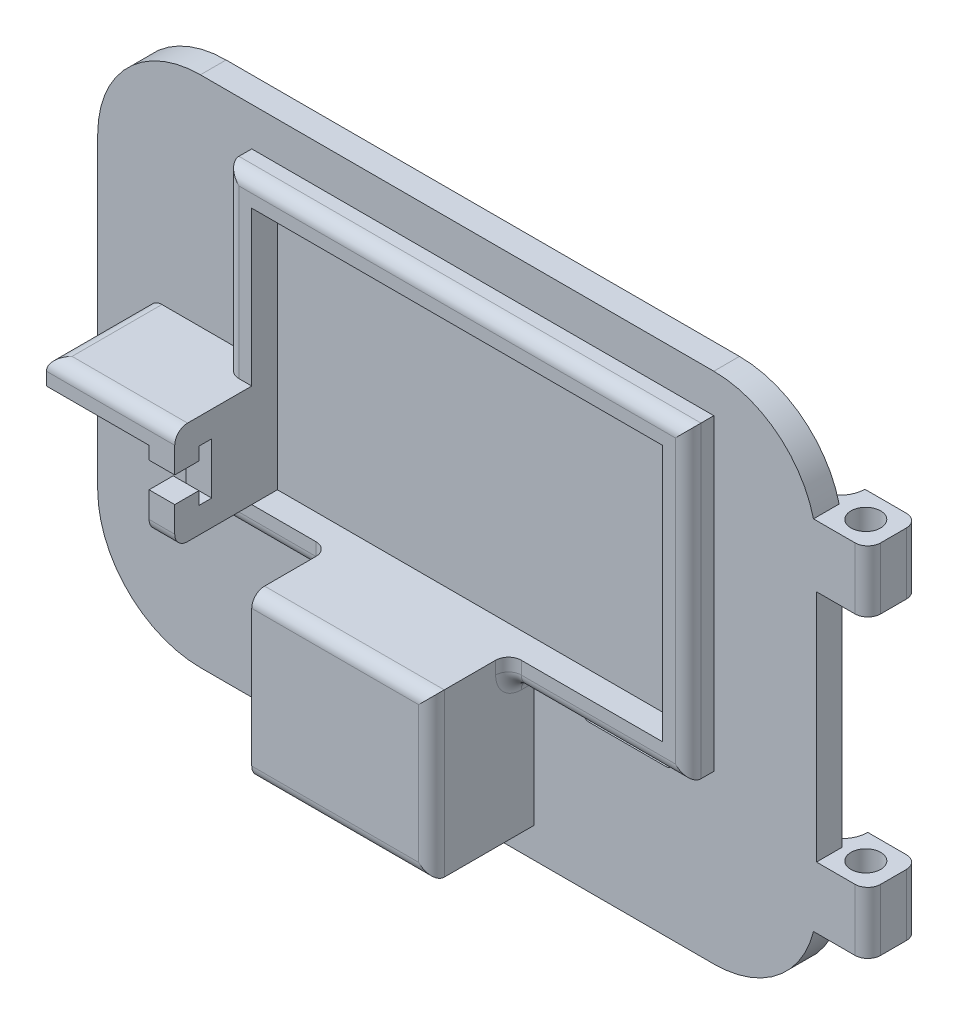
SolidWorks part; units mm, degrees
ref_plane "Front Plane" through (0, 0, 0) normal (0, 0, 1) x (1, 0, 0)
ref_plane "Top Plane" through (0, 0, 0) normal (0, 1, 0) x (1, 0, 0)
ref_plane "Right Plane" through (0, 0, 0) normal (1, 0, 0) x (0, 0, -1)
sketch "Sketch1" plane through (0, 0, 0) normal (0, 0, 1) x (1, 0, 0)
  line L0 (-63.5, 63.5) -> (63.5, 63.5)
  line L1 (63.5, -63.5) -> (-63.5, -63.5)
  line L2 (-88.9, -38.1) -> (-88.9, 38.1)
  line L3 (88.9, -38.1) -> (88.9, 38.1)
  arc A0 (-88.9, 38.1) -> (-63.5, 63.5) centre (-63.5, 38.1) cw
  arc A1 (-63.5, -63.5) -> (-88.9, -38.1) centre (-63.5, -38.1) cw
  arc A2 (63.5, -63.5) -> (88.9, -38.1) centre (63.5, -38.1) ccw
  arc A3 (88.9, 38.1) -> (63.5, 63.5) centre (63.5, 38.1) ccw
  dimension "D1" = 25.4
  dimension "D2" = 88.9
  dimension "D3" = 88.9
  dimension "D4" = 63.5
  dimension "D5" = 63.5
extrude "Boss-Extrude1" add sketch "Sketch1" against normal blind 6.35
sketch "Sketch3" plane through (0, 0, 0) normal (0, 0, 1) x (1, 0, 0)
  line L0 (63.5, 63.5) -> (88.9, 63.5) construction
  line L1 (88.9, 63.5) -> (101.6, 63.5) construction
  line L6 (101.6, 28.956) -> (101.6, 44.196)
  line L8 (101.6, 44.196) -> (88.1576, 44.196)
  line L9 (101.6, 63.5) -> (101.6, 28.956) construction
  line L10 (101.6, 28.956) -> (88.9, 28.956)
  line L11 (88.9, -38.1) -> (88.9, 38.1) construction
  line L12 (88.9, 28.956) -> (88.9, 38.1)
  arc A0 (88.9, 38.1) -> (88.1576, 44.196) centre (63.5, 38.1) ccw
  dimension "D5" = 25.4
  dimension "D1" = 25.4
  dimension "D2" = 12.7
  dimension "D3" = 34.544
  dimension "D4" = 19.304
extrude "Boss-Extrude2" add sketch "Sketch3" against normal blind 12.7
sketch "Sketch4" plane through (0, 44.196, 0) normal (0, 1, 0) x (1, 0, 0)
  line L0 (101.6, 6.35) -> (94.75, 6.35) construction
  line L1 (101.6, 12.7) -> (101.6, 0) construction
  circle A0 centre (94.75, 6.35) radius 3.675
  point P6 (98.425, 6.35)
  dimension "D1" = 7.35
  dimension "D2" = 3.175
extrude "Cut-Extrude2" cut sketch "Sketch4" against normal up to next
sketch "Sketch5" plane through (0, 0, 0) normal (0, 0, 1) x (1, 0, 0)
  line L0 (0, 0) -> (88.9402, 0)
mirror "Mirror1" about plane through (0, 0, 0) normal (0, 1, 0) of "Cut-Extrude2", "Boss-Extrude2"
sketch "Sketch7" plane through (0, 0, -6.35) normal (0, 0, -1) x (-1, 0, 0)
  line L0 (0, 0) -> (57.15, 0) construction
  point P4 (57.15, 0)
  dimension "D1" = 57.15
ref_plane "Plane1" through (-57.15, 0, -6.35) normal (-1, 0, 0) x (0, 0, 1)
sketch "Sketch8" plane through (-57.15, 0, -6.35) normal (-1, 0, 0) x (0, 0, 1)
  line L0 (0, 0) -> (0, 38.1) construction
  line L1 (0, 38.1) -> (0, 44.45)
  line L2 (-19.05, 25.4) -> (-19.05, -25.4)
  line L3 (0, 24.7494) -> (-24.0575, 24.7494) construction
  line L4 (-12.7, 25.4) -> (-12.7, 40.5526) construction
  line L5 (-19.05, 0) -> (-12.7, 0) construction
  line L6 (-12.7, -25.4) -> (-12.7, 25.4)
  line L7 (0, -38.1) -> (0, -44.45)
  arc A0 (0, 44.45) -> (-19.05, 25.4) centre (0, 25.4) ccw
  arc A1 (0, 38.1) -> (-12.7, 25.4) centre (0, 25.4) ccw
  arc A2 (0, -38.1) -> (-12.7, -25.4) centre (0, -25.4) cw
  arc A3 (0, -44.45) -> (-19.05, -25.4) centre (0, -25.4) cw
  dimension "D1" = 38.1
  dimension "D2" = 6.35
  dimension "D3" = 19.7006
  dimension "D4" = 12.7
extrude "Boss-Extrude3" add sketch "Sketch8" against normal blind 12.7
fillet "Fillet1" radius 6.35 1 edges at (-50.8, -44.45, -6.35)
fillet "Fillet2" radius 6.35 1 edges at (-57.15, -44.0467, -6.35)
fillet "Fillet3" radius 6.35 1 edges at (-44.45, -44.0467, -6.35)
fillet "Fillet4" radius 6.35 3 edges at (-50.8, 44.45, -6.35) (-44.45, 41.275, -6.35) (-57.15, 41.275, -6.35)
sketch "Sketch9" plane through (0, 0, 0) normal (0, 0, 1) x (1, 0, 0)
  line L0 (88.9402, 0) -> (-88.9, 0) construction
  line L1 (-88.9, 38.1) -> (-88.9, -38.1) construction
  line L22 (57.15, 47.625) -> (-44.45, 47.625)
  line L23 (57.15, 47.625) -> (57.15, -15.875)
  line L24 (57.15, -15.875) -> (-44.45, -15.875)
  line L25 (-44.45, 47.625) -> (-44.45, -15.875)
  line L26 (-63.5, -63.5) -> (63.5, -63.5) construction
  line L28 (63.5, 53.975) -> (63.5, -22.225)
  line L29 (63.5, -22.225) -> (-50.8, -22.225)
  line L30 (-50.8, 53.975) -> (-50.8, -22.225)
  line L31 (63.5, 53.975) -> (-50.8, 53.975)
  dimension "D1" = 63.5
  dimension "D2" = 101.6
  dimension "D3" = 47.625
  dimension "D4" = 38.1
  dimension "D5" = 6.35
extrude "Boss-Extrude4" add sketch "Sketch9" along normal blind 6.35
sketch "Sketch10" plane through (0, 0, 0) normal (0, 0, 1) x (1, 0, 0)
  line L0 (-44.45, 47.625) -> (-44.45, 10.9459) construction
  line L1 (57.15, -15.875) -> (57.15, -25.527) construction
  line L2 (32.639, -25.527) -> (51.689, -25.527) construction
  line L3 (32.639, -23.9395) -> (51.689, -23.9395)
  line L4 (32.639, -27.1145) -> (51.689, -27.1145)
  line L5 (57.15, -25.527) -> (42.164, -25.527) construction
  arc A0 (32.639, -23.9395) -> (32.639, -27.1145) centre (32.639, -25.527) ccw
  arc A1 (51.689, -27.1145) -> (51.689, -23.9395) centre (51.689, -25.527) ccw
  point P6 (42.164, -25.527)
  dimension "D1" = 9.652
  dimension "D2" = 14.986
  dimension "D3" = 19.05
  dimension "D4" = 3.175
extrude "Cut-Extrude3" cut sketch "Sketch10" against normal up to next
sketch "Sketch14" plane through (0, 0, 0) normal (0, 0, 1) x (1, 0, 0)
  line L0 (12.7, -22.225) -> (12.7, -49.657)
  line L1 (-50.8, -22.225) -> (63.5, -22.225) construction
  line L2 (12.7, -49.657) -> (-25.4, -49.657)
  line L3 (63.5, -22.225) -> (63.5, 53.975) construction
  line L4 (19.05, -22.225) -> (19.05, -56.007)
  line L5 (19.05, -56.007) -> (-25.4, -56.007)
  line L6 (-25.4, -56.007) -> (-25.4, -49.657)
  line L7 (19.05, -15.875) -> (-25.4, -15.875)
  line L8 (-44.45, -15.875) -> (57.15, -15.875) construction
  line L9 (-25.4, -15.875) -> (-25.4, -22.225)
  line L10 (-25.4, -22.225) -> (12.7, -22.225)
  line L11 (19.05, -22.225) -> (19.05, -15.875)
  dimension "D1" = 38.1
  dimension "D2" = 27.432
  dimension "D3" = 50.8
  dimension "D4" = 6.35
extrude "Boss-Extrude7" add sketch "Sketch14" along normal blind 25.4
sketch "Sketch15" plane through (0, -49.657, 0) normal (0, 1, 0) x (1, 0, 0)
  line L0 (-25.4, -25.4) -> (-25.4, -19.05)
  line L1 (-25.4, -25.4) -> (-25.4, 0) construction
  line L2 (-25.4, -19.05) -> (12.7, -19.05)
  line L3 (12.7, -25.4) -> (12.7, 0) construction
  line L4 (12.7, -19.05) -> (12.7, -25.4)
  line L5 (12.7, -25.4) -> (-25.4, -25.4)
  dimension "D1" = 6.35
extrude "Boss-Extrude8" add sketch "Sketch15" along normal up to next
sketch "Sketch16" plane through (0, 0, 0) normal (0, 0, 1) x (1, 0, 0)
  line L0 (-50.8, 3.175) -> (-76.2, 3.175)
  line L1 (-50.8, 53.975) -> (-50.8, -22.225) construction
  line L2 (63.5, 53.975) -> (-50.8, 53.975) construction
  line L3 (-76.2, 9.525) -> (-76.2, 3.175)
  line L4 (-50.8, 9.525) -> (-44.45, 9.525)
  line L5 (-44.45, 47.625) -> (-44.45, -15.875) construction
  line L6 (-44.45, 9.525) -> (-44.45, -15.875)
  line L7 (-44.45, -15.875) -> (-50.8, -15.875)
  line L8 (-50.8, -15.875) -> (-50.8, 3.175)
  line L9 (-44.45, -15.875) -> (-25.4, -15.875) construction
  line L13 (-50.8, 9.525) -> (-76.2, 9.525)
  point P8 (-47.625, -15.875)
  dimension "D1" = 25.4
  dimension "D2" = 50.8
  dimension "D3" = 6.35
extrude "Boss-Extrude9" add sketch "Sketch16" along normal blind 25.4
sketch "Sketch17" plane through (-50.8, 0, 0) normal (-1, 0, 0) x (0, 0, 1)
  line L0 (0, 3.175) -> (16.256, 3.175) construction
  line L1 (0, 3.175) -> (25.4, 3.175) construction
  line L2 (16.256, 3.175) -> (16.256, -9.525)
  line L3 (16.256, -9.525) -> (19.431, -9.525)
  line L4 (19.431, -9.525) -> (19.431, 3.175)
  line L5 (19.431, 3.175) -> (16.256, 3.175)
  dimension "D1" = 16.256
  dimension "D2" = 12.7
  dimension "D3" = 3.175
extrude "Cut-Extrude4" cut sketch "Sketch17" against normal up to next
sketch "Sketch18" plane through (0, 0, 25.4) normal (0, 0, 1) x (1, 0, 0)
  line L0 (-50.8, 0) -> (-44.45, 0) construction
  line L1 (-44.45, -15.875) -> (-44.45, 9.525) construction
  line L4 (-50.8, 3.175) -> (-50.8, -15.875) construction
  line L5 (-44.45, 0) -> (-50.8, 0)
  line L6 (-44.45, 0) -> (-44.45, -6.35)
  line L7 (-44.45, -6.35) -> (-50.8, -6.35)
  line L8 (-50.8, 0) -> (-50.8, -6.35)
  line L9 (-44.45, 0) -> (-50.8, -6.35) construction
  line L10 (-44.45, -6.35) -> (-50.8, 0) construction
  line L11 (-44.45, 47.625) -> (-44.45, -15.875) construction
  line L12 (-76.2, 3.175) -> (-50.8, 3.175) construction
  dimension "D1" = 6.35
  dimension "D2" = 3.175
extrude "Cut-Extrude5" cut sketch "Sketch18" against normal up to next
fillet "Fillet6" radius 3.175 16 edges at (19.05, -35.941, 25.4) (-3.175, -15.875, 25.4) (-3.175, -56.007, 25.4) (-25.4, -22.225, 12.7) (19.05, -22.225, 3.175) (-50.8, 31.75, 6.35) (-50.8, -19.05, 6.35) (-38.1, -22.225, 6.35) (41.275, -22.225, 6.35) (63.5, 15.875, 6.35) (6.35, 53.975, 6.35) (-25.4, -19.05, 6.35) (19.05, -19.05, 6.35) (-76.2, 9.525, 12.7) (-60.325, 9.525, 25.4) (-47.625, -15.875, 25.4)
fillet "Fillet9" radius 6.35 4 edges at (88.9, -33.528, -6.35) (88.9, 33.528, -6.35) (88.7137, -41.1705, -6.35) (88.7137, 41.1705, -6.35)
fillet "Fillet10" radius 3.175 4 edges at (101.6, 36.576, -12.7) (101.6, 36.576, 0) (101.6, -36.576, 0) (101.6, -36.576, -12.7)
